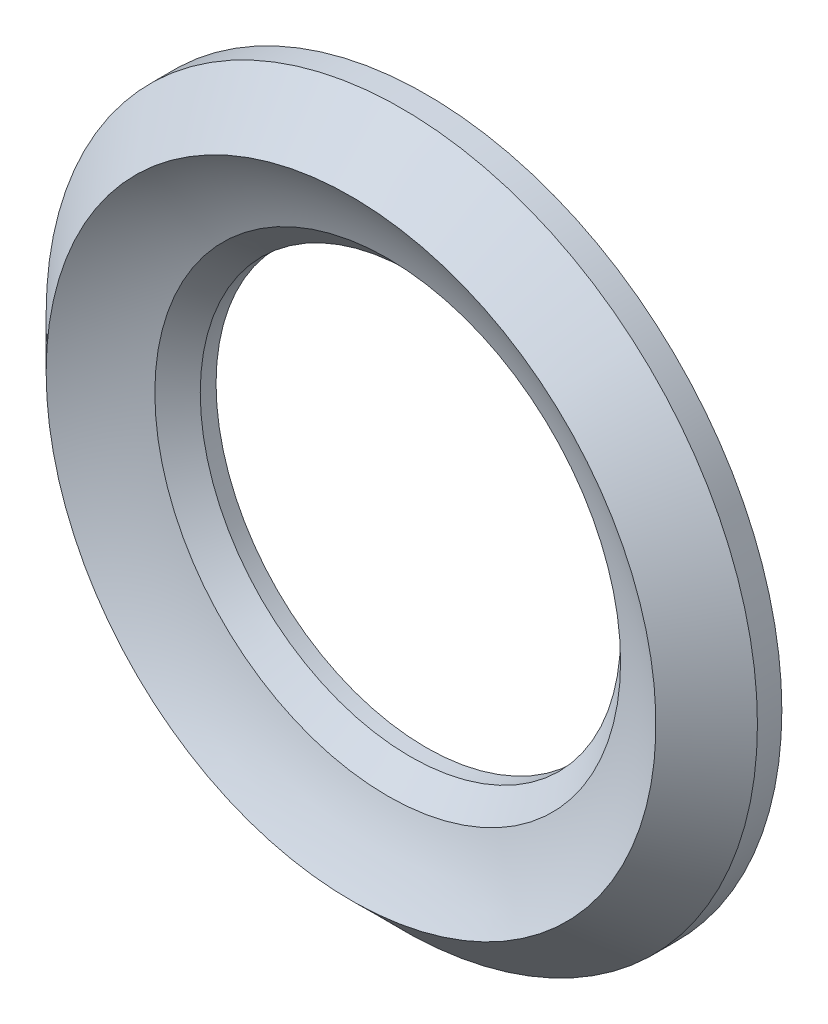
SolidWorks part; units mm, degrees
material "PVC hart"
ref_plane "Ebene vorne" through (0, 0, 0) normal (0, 0, 1) x (1, 0, 0)
ref_plane "Ebene oben" through (0, 0, 0) normal (0, 1, 0) x (1, 0, 0)
ref_plane "Ebene rechts" through (0, 0, 0) normal (1, 0, 0) x (0, 0, -1)
sketch "Skizze2" plane through (0, 0, 0) normal (1, 0, 0) x (0, 0, -1)
  line L0 (-4, 22) -> (-5.5101, 22)
  line L1 (-5.5101, 22) -> (-8.6509, 18.8591)
  line L2 (-4, 13) -> (-4, 0) construction
  line L3 (-6, 22.5) -> (-9.0731, 19.4269) construction
  line L4 (-7.0805, 20.4296) -> (-7.5755, 20.9245) construction
  line L6 (-4, 22) -> (-4, 13)
  line L7 (-4, 13) -> (-5.9773, 13)
  line L8 (0, 0) -> (-19.9192, 0) construction
  line L9 (5.5, 22) -> (3.5, 22) construction
  line L10 (-4, 20) -> (-4, 0) construction
  line L18 (5.5, 13) -> (3.5, 13) construction
  arc A0 (-8.6509, 18.8591) -> (-5.9773, 13) centre (-22.5, 9) cw
  arc A2 (-9.0731, 19.4269) -> (-14.0334, 23.7417) centre (-22.5, 9) ccw construction
  dimension "D1" = 0.7
revolve "Rotation1" add sketch "Skizze2" angle 360 about L8
hole_wizard "Formsenkung für M3 Senkschraube mit Innensechskant1" positions "Skizze3" profile "Skizze4" countersink size "M3" standard "DIN"
sketch "Skizze3" plane through (0, 0, -5.5) normal (0, 0, -1) x (-1, 0, 0)
  line L0 (0, 0) -> (0, 13) construction
  line L2 (-6.697, 16.1679) -> (0, 0) construction
  line L4 (-16.1679, 6.697) -> (0, 0) construction
  line L6 (0, 13) -> (0, 17.5) construction
  line L7 (0, 17.5) -> (0, 20) construction
  circle A0 centre (0, 0) radius 17.5 construction
  point P0 (6.697, 16.1679)
  point P2 (-16.1679, 6.697)
  point P4 (-6.697, 16.1679)
  point P6 (16.1679, 6.697)
sketch "Skizze4" plane through (-6.697, 16.1679, -5.5) normal (1, 0, 0) x (0, 1, 0)
  line L0 (0, 0) -> (0, 12.4807)
  line L1 (0, 12.4807) -> (0.8, 12)
  line L2 (0.8, 12) -> (0.8, 1.15)
  line L3 (0.8, 1.15) -> (1.95, 0)
  line L4 (1.95, 0) -> (0, 0)
  line L5 (-0.8, 1.15) -> (-1.95, 0) construction
  line L6 (0, 12.4807) -> (-0.8, 12) construction
  line L7 (0, -6.35) -> (0, 107.95) construction
  dimension "Bohrerdurchmesser" = 1.6
  dimension "Bohrungstiefe" = 12
  dimension "Senkdurchmesser (Oben)" = 3.9
  dimension "Senkwinkel (Oben)" = 90
  dimension "Spitzenwinkel" = 118
mirror "Spiegeln1" about plane through (0, 0, 0) normal (0, 1, 0) of "Formsenkung für M3 Senkschraube mit Innensechskant1"
chamfer "Fase2" distance 1 angle 45 1 edges at (-13, 0, 5.9773) first distance on face at (-13, 0, 4)
